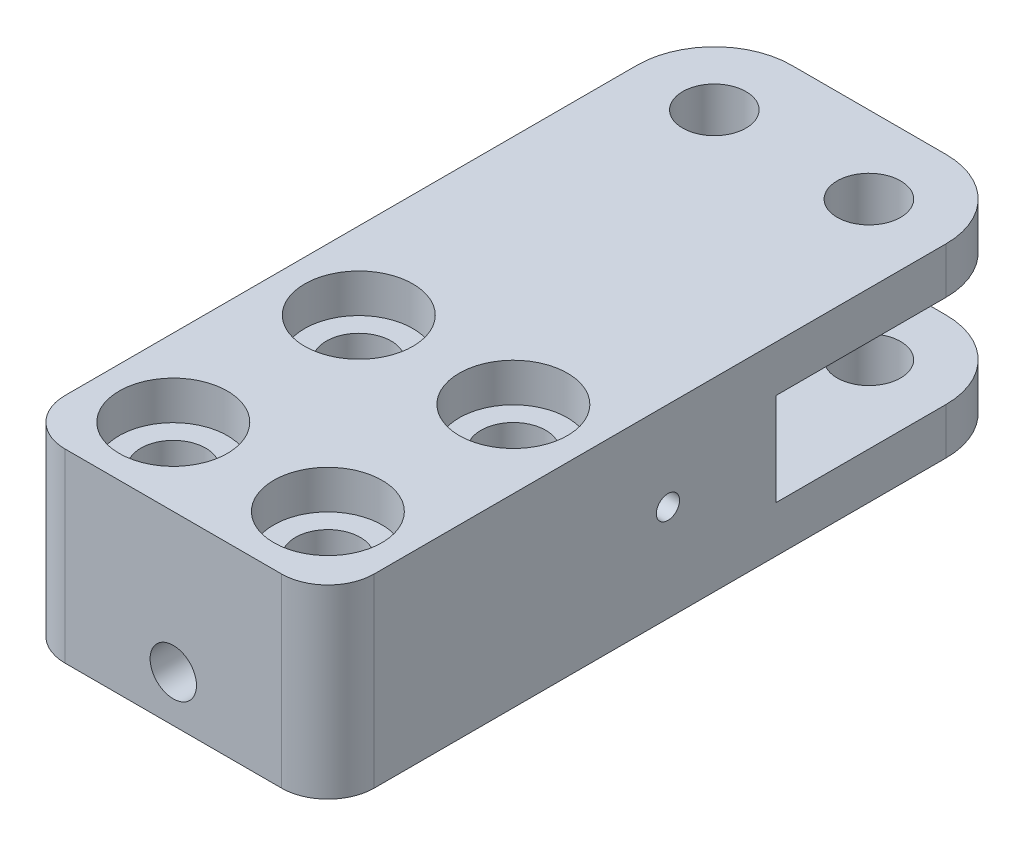
SolidWorks part; units mm, degrees
ref_plane "Front Plane" through (0, 0, 0) normal (0, 0, 1) x (1, 0, 0)
ref_plane "Top Plane" through (0, 0, 0) normal (0, 1, 0) x (1, 0, 0)
ref_plane "Right Plane" through (0, 0, 0) normal (1, 0, 0) x (0, 0, -1)
sketch "Sketch1" plane through (0, 0, 0) normal (0, 1, 0) x (1, 0, 0)
  line L1 (10, -522) -> (-10, -522)
  line L2 (10, -522) -> (10, -567)
  line L3 (10, -567) -> (-10, -567)
  line L4 (-10, -522) -> (-10, -567)
  dimension "D1" = 45
  dimension "D2" = 10
  dimension "D3" = 567
  dimension "D4" = 20
extrude "Boss-Extrude1" add sketch "Sketch1" along normal blind 12 from offset 11
sketch "Sketch2" plane through (0, 23, 0) normal (0, 1, 0) x (1, 0, 0)
  line L0 (-5, -550) -> (5, -550) construction
  line L1 (5, -550) -> (5, -562) construction
  line L2 (5, -562) -> (-5, -562) construction
  line L3 (-5, -562) -> (-5, -550) construction
  line L4 (0, -550) -> (0, -562) construction
  line L5 (10, -567) -> (10, -522) construction
  line L6 (-10, -567) -> (10, -567) construction
  circle A0 centre (-5, -562) radius 2.1
  circle A1 centre (5, -562) radius 2.1
  circle A2 centre (-5, -550) radius 2.1
  circle A3 centre (5, -550) radius 2.1
  dimension "D1" = 4.2
  dimension "D2" = 4.2
  dimension "D3" = 4.2
  dimension "D4" = 4.2
  dimension "D5" = 10
  dimension "D6" = 12
  dimension "D7" = 10
  dimension "D8" = 5
extrude "Cut-Extrude1" cut sketch "Sketch2" against normal blind 16
sketch "Sketch3" plane through (10, 0, 0) normal (1, 0, 0) x (0, 0, -1)
  line L0 (-522, 23) -> (-522, 11) construction
  line L1 (-522, 20) -> (-538, 20)
  line L2 (-522, 20) -> (-522, 14)
  line L3 (-522, 14) -> (-538, 14)
  line L4 (-538, 20) -> (-538, 14)
  line L5 (-567, 23) -> (-522, 23) construction
  dimension "D1" = 6
  dimension "D2" = 3
  dimension "D3" = 16
extrude "Cut-Extrude2" cut sketch "Sketch3" against normal blind 20
sketch "Sketch4" plane through (0, 23, 0) normal (0, 1, 0) x (1, 0, 0)
  line L0 (10, -567) -> (10, -522) construction
  line L2 (10, -522) -> (-10, -522) construction
  circle A0 centre (-5, -527) radius 2.05
  circle A1 centre (5, -527) radius 2.05
  dimension "D1" = 4.1
  dimension "D2" = 4.1
  dimension "D3" = 10
  dimension "D4" = 5
  dimension "D5" = 5
  dimension "D6" = 5
extrude "Cut-Extrude3" cut sketch "Sketch4" against normal blind 13
fillet "Fillet1" radius 5 4 edges at (10, 12.5, 522) (10, 21.5, 522) (-10, 12.5, 522) (-10, 21.5, 522)
sketch "Sketch5" plane through (0, 23, 0) normal (0, 1, 0) x (1, 0, 0)
  circle A0 centre (-5, -550) radius 3.5
  circle A1 centre (5, -550) radius 3.5
  circle A2 centre (-5, -562) radius 3.5
  circle A3 centre (5, -562) radius 3.5
  dimension "D1" = 7
  dimension "D2" = 7
  dimension "D3" = 7
  dimension "D4" = 7
extrude "Cut-Extrude4" cut sketch "Sketch5" against normal blind 2.5
fillet "Fillet2" radius 3 2 edges at (10, 17, 567) (-10, 17, 567)
sketch "Sketch6" plane through (0, 11, 0) normal (0, -1, 0) x (1, 0, 0)
  line L0 (0, 532) -> (0, 522) construction
  line L1 (-1.75, 549) -> (1.75, 549)
  line L2 (-1.75, 549) -> (-1.75, 532)
  line L3 (-1.75, 532) -> (1.75, 532)
  line L4 (1.75, 549) -> (1.75, 532)
  line L5 (5, 522) -> (-5, 522) construction
  dimension "D1" = 3.5
  dimension "D2" = 17
  dimension "D3" = 10
extrude "Cut-Extrude5" cut sketch "Sketch6" against normal blind 9
sketch "Sketch7" plane through (-10, 0, 0) normal (-1, 0, 0) x (0, 0, 1)
  line L0 (527, 20) -> (538, 20) construction
  line L1 (538, 14) -> (527, 14) construction
  line L2 (538, 20) -> (538, 14) construction
  circle A0 centre (545, 17.25) radius 0.75
  dimension "D1" = 1.5
  dimension "D2" = 2.75
  dimension "D3" = 3.25
  dimension "D4" = 7
extrude "Cut-Extrude6" cut sketch "Sketch7" against normal blind 20
sketch "Sketch8" plane through (0, 0, 567) normal (0, 0, 1) x (1, 0, 0)
  line L0 (-7, 11) -> (7, 11) construction
  circle A0 centre (0, 14) radius 1.5
  dimension "D1" = 3
  dimension "D2" = 3
extrude "Cut-Extrude7" cut sketch "Sketch8" against normal blind 18
